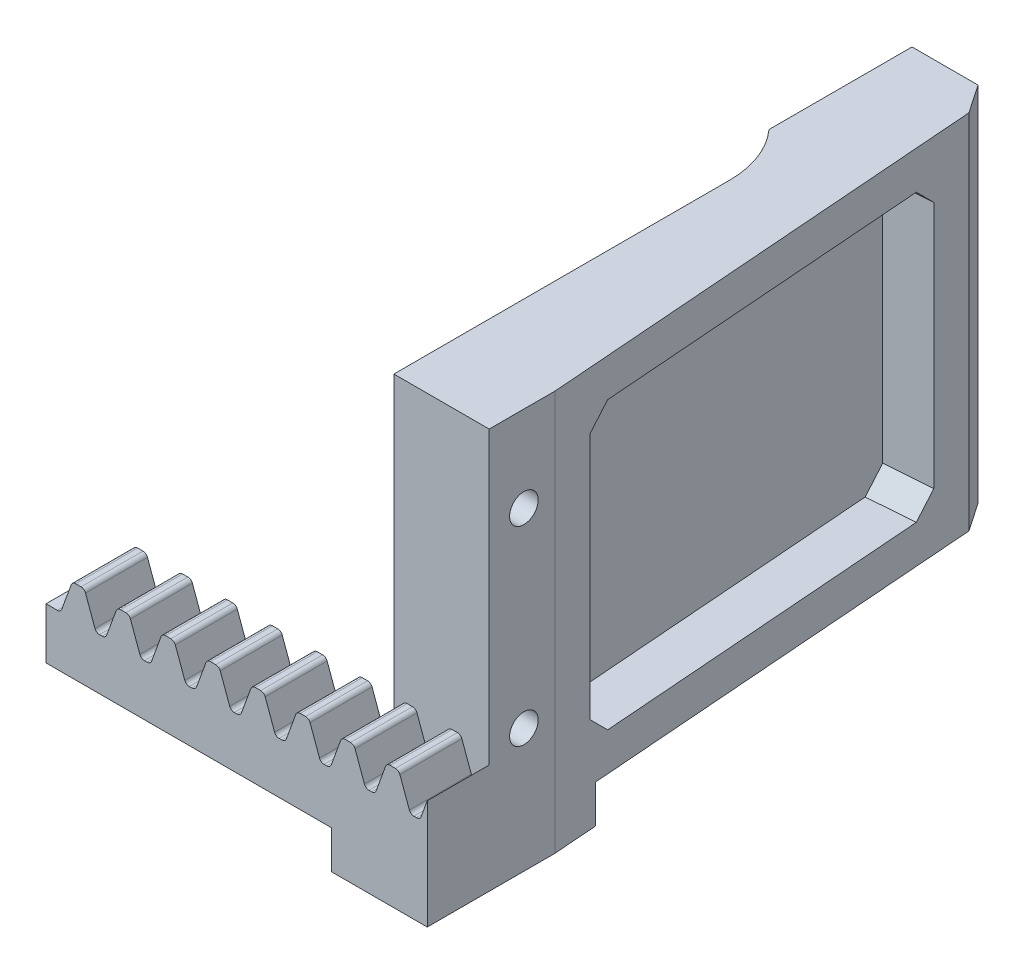
SolidWorks part; units mm, degrees
ref_plane "Front Plane" through (0, 0, 0) normal (0, 0, 1) x (1, 0, 0)
ref_plane "Top Plane" through (0, 0, 0) normal (0, 1, 0) x (1, 0, 0)
ref_plane "Right Plane" through (0, 0, 0) normal (1, 0, 0) x (0, 0, -1)
sketch "Sketch1" plane through (0, 0, 0) normal (0, 0, 1) x (1, 0, 0)
  line L0 (-100, 7.5) -> (-100, -7.5) construction
  line L1 (-100, -7.5) -> (100, -7.5) construction
  line L2 (100, -7.5) -> (100, 7.5) construction
  line L4 (0, 7.5) -> (0, -7.5) construction
  line L5 (-100, 6) -> (100, 6) construction
  line L6 (-97.2361, 7.5) -> (-95.9718, 7.5) construction
  line L7 (-95.9718, 7.5) -> (-94.7434, 4.125) construction
  line L8 (-97.2361, 7.5) -> (-98.4645, 4.125) construction
  line L9 (-98.4645, 4.125) -> (-94.7434, 4.125) construction
  line L10 (-96.604, 7.5) -> (-96.604, 4.125) construction
  line L11 (-100, 0) -> (-87.1792, 0) construction
  line L12 (100, 0) -> (87.1792, 0) construction
  point P15 (-91.8916, 7.5)
  point P16 (-21, -7.5)
  point P17 (-95.4259, 6)
  point P18 (-97.7821, 6)
  point P21 (-0.75, -7.5)
  dimension "Length" = 200
  dimension "Height" = 15
  dimension "Number of Teeth" = 42
  dimension "Pressure Angle" = 20
  dimension "Circular Pitch" = 4.7124
  dimension "Addendum" = 1.5
  dimension "Dedendum" = 1.875
  dimension "Circular Tooth Thickness" = 2.3562
  dimension "Rack Length" = 193.2079
  dimension "D1" = 9.4248
  dimension "For Module" = 1.5
sketch "Sketch2" plane through (0, 0, 0) normal (1, 0, 0) x (0, 0, -1)
  line L0 (-7.5, 0) -> (7.5, 0) construction
  dimension "Face Width" = 15
sketch "Sketch3" plane through (0, 0, 0) normal (0, 0, 1) x (1, 0, 0)
  line L1 (-100, 7.5) -> (100, 7.5)
  line L2 (-100, 7.5) -> (-100, -7.5)
  line L3 (-100, -7.5) -> (100, -7.5)
  line L4 (100, 7.5) -> (100, -7.5)
extrude "Boss-Extrude1" add sketch "Sketch3" against normal up to vertex (7.5 mm away) and the other way up to vertex (7.5 mm away) up to point (0, 0, -7.5) other way up to point (0, 0, 7.5)
sketch "Sketch4" plane through (0, 0, 0) normal (0, 0, 1) x (1, 0, 0)
  line L0 (-96.604, 7.5) -> (-91.8916, 7.5) construction
  line L9 (-94.2478, 7.5) -> (-94.2478, 4.125)
  line L10 (-94.2478, 4.125) -> (-94.7434, 4.125)
  line L11 (-94.7434, 4.125) -> (-95.9718, 7.5)
  line L12 (-95.9718, 7.5) -> (-94.2478, 7.5)
  line L13 (-97.2361, 7.5) -> (-98.4645, 4.125)
  line L14 (-98.4645, 4.125) -> (-98.9602, 4.125)
  line L15 (-98.9602, 4.125) -> (-98.9602, 7.5)
  line L16 (-98.9602, 7.5) -> (-97.2361, 7.5)
extrude "Cut-Extrude1" cut sketch "Sketch4" against normal through all both and the other way through all
fillet "Fillet1" radius 0.5033 4 edges at (-98.4645, 4.125, 0) (-94.7434, 4.125, 0) (-95.9718, 7.5, 0) (-97.2361, 7.5, 0)
pattern_linear "LPattern1" count 42 spacing 4.7124 along (1, 0, 0) of "Cut-Extrude1", "Fillet1"
sketch "Sketch5" plane through (0, 0, 0) normal (0, 0, 1) x (1, 0, 0)
  line L0 (-100, 6) -> (-103.6726, 6) construction
  line L1 (-98.9602, 4.125) -> (-103.6726, 4.125)
  line L2 (-98.9602, 4.125) -> (-98.9602, 7.5)
  line L3 (-98.9602, 7.5) -> (-103.6726, 7.5)
  line L4 (-103.6726, 4.125) -> (-103.6726, 7.5)
  line L5 (98.9602, 7.5) -> (103.6726, 7.5)
  line L6 (98.9602, 7.5) -> (98.9602, 4.125)
  line L7 (98.9602, 4.125) -> (103.6726, 4.125)
  line L8 (103.6726, 7.5) -> (103.6726, 4.125)
  line L9 (103.6726, 6) -> (100, 6) construction
  dimension "D1" = 4.7124
extrude "Cut-Extrude2" cut sketch "Sketch5" against normal through all both and the other way through all
sketch "Sketch6" plane through (0, 0, 0) normal (1, 0, 0) x (0, 0, -1)
  line L0 (-7.5, -7.5) -> (-7.5, 4.125) construction
  line L1 (-1, 10.225) -> (12.8906, 10.225)
  line L2 (-1, 10.225) -> (-1, -11.7256)
  line L3 (-1, -11.7256) -> (12.8906, -11.7256)
  line L4 (12.8906, 10.225) -> (12.8906, -11.7256)
  dimension "D1" = 6.5
extrude "Cut-Extrude3" cut sketch "Sketch6" against normal through all both and the other way through all
sketch "Sketch8" plane through (0, 0, 0) normal (0, 0, 1) x (1, 0, 0)
  line L0 (-100, 4.125) -> (-100, -7.5) construction
  line L1 (-60, 29.716) -> (115.1008, 29.716)
  line L2 (-60, 29.716) -> (-60, -15.2308)
  line L3 (-60, -15.2308) -> (115.1008, -15.2308)
  line L4 (115.1008, 29.716) -> (115.1008, -15.2308)
  dimension "D1" = 40
extrude "Cut-Extrude6" cut sketch "Sketch8" against normal through all and the other way through all
sketch "Sketch9" plane through (0, 0, 0) normal (0, 0, 1) x (1, 0, 0)
  line L0 (-86.8994, 7.5) -> (-87.459, 7.5) construction
  line L1 (-104.5799, -1.25) -> (-49.0781, -1.25)
  line L2 (-104.5799, -1.25) -> (-104.5799, -12.034)
  line L3 (-104.5799, -12.034) -> (-49.0781, -12.034)
  line L4 (-49.0781, -1.25) -> (-49.0781, -12.034)
  dimension "D1" = 8.75
extrude "Cut-Extrude7" cut sketch "Sketch9" along normal through all
sketch "Sketch10" plane through (0, 0, 1) normal (0, 0, -1) x (-1, 0, 0)
  line L1 (60, -1.25) -> (70, -1.25)
  line L2 (60, -1.25) -> (60, 36.75)
  line L3 (60, 36.75) -> (70, 36.75)
  line L4 (70, -1.25) -> (70, 36.75)
  dimension "D1" = 38
  dimension "D2" = 10
extrude "Boss-Extrude2" add sketch "Sketch10" along normal blind 6.9
sketch "Sketch11" plane through (0, 0, -5.9) normal (0, 0, -1) x (-1, 0, 0)
  line L0 (100, -1.25) -> (70, -1.25) construction
  line L1 (60, 36.75) -> (72.54, 36.75)
  line L2 (60, 36.75) -> (60, -1.25)
  line L3 (60, -1.25) -> (72.54, -1.25)
  line L4 (72.54, 36.75) -> (72.54, -1.25)
  dimension "D1" = 12.54
extrude "Boss-Extrude3" add sketch "Sketch11" along normal blind 50
sketch "Sketch12" plane through (0, -1.25, 0) normal (0, -1, 0) x (1, 0, 0)
  line L0 (-60, -55.9) -> (-72.54, -55.9) construction
  line L1 (-72.54, -5.9) -> (-70, -5.9)
  line L2 (-72.54, -5.9) -> (-72.54, -40.9)
  line L3 (-72.54, -40.9) -> (-70, -40.9)
  line L4 (-70, -5.9) -> (-70, -40.9)
  line L5 (-70, -5.9) -> (-70, 1) construction
  line L6 (-60, -5.9) -> (-63.8, -55.9)
  line L7 (-60, 7.5) -> (-60, -55.9) construction
  line L8 (-63.8, -55.9) -> (-60, -55.9)
  line L9 (-60, -55.9) -> (-60, -5.9)
  dimension "D1" = 15
  dimension "D2" = 3.8
extrude "Cut-Extrude8" cut sketch "Sketch12" against normal through all
chamfer "Chamfer1" distance 3 angle 30 1 edges at (-63.8, 17.75, -55.9) first distance on face at (-61.9, 17.75, -30.9)
fillet "Fillet2" radius 10 1 edges at (-70, 17.75, -40.9)
sketch "Sketch13" plane through (-59.2096, 0, 4.4999) normal (0.9971, 0, -0.0758) x (-0.0758, 0, -0.9971)
  line L8 (14.4299, 2.75) -> (53.5741, 2.75)
  line L9 (53.5741, 2.75) -> (53.5741, 32.75)
  line L10 (53.5741, 32.75) -> (14.4299, 32.75)
  line L11 (14.4299, 32.75) -> (14.4299, 2.75)
  line L12 (14.4299, 2.75) -> (53.5741, 2.75)
  line L13 (53.5741, 2.75) -> (53.5741, 32.75)
  line L14 (53.5741, 32.75) -> (14.4299, 32.75)
  line L15 (14.4299, 32.75) -> (14.4299, 2.75)
  dimension "D1" = 4
extrude "Cut-Extrude9" cut sketch "Sketch13" against normal blind 5
chamfer "Chamfer2" distance 2 angle 45 4 edges at (-62.7959, 2.75, -9.699) (-65.7623, 2.75, -48.7307) (-65.7623, 32.75, -48.7307) (-62.7959, 32.75, -9.699)
sketch "Sketch14" plane through (-60, 0, 0) normal (1, 0, 0) x (0, 0, -1)
  line L0 (5.9, 36.75) -> (5.9, -1.25) construction
  line L1 (5.9, 36.75) -> (-1, 36.75) construction
  line L2 (-7.5, -1.25) -> (5.9, -1.25) construction
  circle A0 centre (2.64, 27.75) radius 1.5
  circle A1 centre (2.64, 7.75) radius 1.5
  dimension "D1" = 3
  dimension "D2" = 3.26
  dimension "D3" = 9
  dimension "D4" = 9
  dimension "D5" = 3.26
extrude "Cut-Extrude10" cut sketch "Sketch14" against normal through all
sketch "Sketch15" plane through (0, -1.25, 0) normal (0, -1, 0) x (1, 0, 0)
  line L0 (-70.0697, 7.5) -> (-70, -10.5)
  line L3 (-60, -5.9) -> (-60, 7.5)
  line L4 (-60, 7.5) -> (-60, -5.9) construction
  line L5 (-60, 7.5) -> (-100, 7.5) construction
  line L6 (-60, 7.5) -> (-70.0697, 7.5)
  line L9 (-60, -5.9) -> (-63.5727, -52.9086) construction
  line L10 (-60, -5.9) -> (-60.3496, -10.5)
  line L12 (-70, -10.5) -> (-67.1748, -10.5)
  line L13 (-67.1748, -10.5) -> (-67.1748, 5.1375)
  line L14 (-67.1748, 5.1375) -> (-63.1748, 5.1375)
  line L15 (-63.1748, 5.1375) -> (-63.1748, -10.5)
  line L16 (-63.1748, -10.5) -> (-60.3496, -10.5)
  line L17 (-70, -34.2405) -> (-70, 1) construction
  point P3 (-70, -10.5)
  point P16 (0, 0)
  dimension "D1" = 18
  dimension "D2" = 4
extrude "Boss-Extrude4" add sketch "Sketch15" along normal blind 4 and the other way blind 1
fillet "Fillet3" radius 0.25 2 edges at (-63.1748, -3.25, 5.1375) (-67.1748, -3.25, 5.1375)
fillet "Fillet4" radius 1 2 edges at (-63.1748, -3.25, -10.5) (-67.1748, -3.25, -10.5)
equation "\"Diametral Pitch\"= 1 / \"Module\""
equation "\"Pressure Angle\"=20"
equation "\"Dedendum\"= 1.25 / \"Diametral Pitch\""
equation "\"Addendum\"= 1 / \"Diametral Pitch\""
equation "\"WorkingDepth\"= 2 / \"Diametral Pitch\""
equation "\"WholeDepth\"= 2.25 / \"Diametral Pitch\""
equation "\"Clearance\"= 0.25 / \"Diametral Pitch\""
equation "\"ToothThickness\"= ( pi / 2 ) / \"Diametral Pitch\""
equation "\"CircularPitch\"= pi / \"Diametral Pitch\""
equation "\"Fillet\"= \"Clearance\" * cos ( \"Pressure Angle\" ) * tan ( ( 90 + \"Pressure Angle\" ) / 2 )"
equation "\"Module\"= 1.5"
equation "\"Addendum@Sketch1\"=\"Addendum\""
equation "\"Pressure Angle@Sketch1\"=\"Pressure Angle\""
equation "\"Dedendum@Sketch1\"=\"Dedendum\""
equation "\"Circular Pitch@Sketch1\"=\"CircularPitch\""
equation "\"Circular Tooth Thickness@Sketch1\"=\"ToothThickness\""
equation "\"Number of Teeth@Sketch1\"=int(\"Length@Sketch1\"/(2*\"Circular Tooth Thickness@Sketch1\"))"
equation "\"Rack Length@Sketch1\"=\"Circular Pitch@Sketch1\"*(\"Number of Teeth@Sketch1\"-1)"
equation "\"D3@LPattern1\"=\"CircularPitch\""
equation "\"D1@LPattern1\"=\"Number of Teeth@Sketch1\""
equation "\"D1@Sketch1\"=\"Circular Pitch@Sketch1\"*2"
equation "\"D1@Fillet1\"=\"Fillet\""
equation "\"For Module@Sketch1\"=\"Module\""
equation "\"D4@LPattern1\"=\"CircularPitch\""
equation "\"D1@Sketch5\"=\"CircularPitch\""
